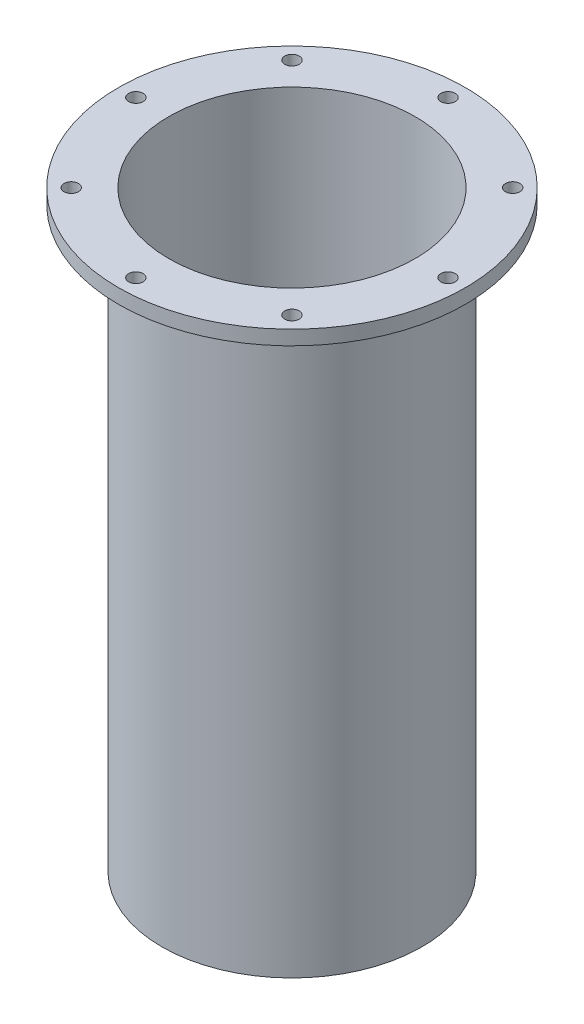
SolidWorks part; units mm, degrees
ref_plane "Front Plane" through (0, 0, 0) normal (0, 0, 1) x (1, 0, 0)
ref_plane "Top Plane" through (0, 0, 0) normal (0, 1, 0) x (1, 0, 0)
ref_plane "Right Plane" through (0, 0, 0) normal (1, 0, 0) x (0, 0, -1)
ref_axis "Axial" through (0, 55, 0) along (0, -1, 0)
sketch "Sketch1" plane through (0, 0, 0) normal (0, 1, 0) x (1, 0, 0)
  circle A0 centre (0, 0) radius 54.102
  circle A1 centre (0, 0) radius 57.15
  dimension "D1" = 114.3
  dimension "D2" = 108.204
extrude "Scheduled Chamber" add sketch "Sketch1" against normal blind 260.35
sketch "Sketch2" plane through (0, 0, 0) normal (0, 1, 0) x (1, 0, 0)
  circle A0 centre (0, 0) radius 54.102
  circle A1 centre (0, 0) radius 76.2
  dimension "D1" = 152.4
  dimension "D2" = 108.204
extrude "Flange" add sketch "Sketch2" against normal blind 6.35
sketch "Sketch3" plane through (0, 0, 0) normal (0, 1, 0) x (1, 0, 0)
  line L0 (0, -83.82) -> (0, 83.82) construction
  circle A0 centre (0, 68.58) radius 3.175
  dimension "D1" = 6.35
  dimension "D2" = 68.58
extrude "Original Bolt Hole" cut sketch "Sketch3" against normal up to next
pattern_circular "Bolt Hole Pattern" count 8 over 360 about axis through (0, 55, 0) along (0, -1, 0) of "Original Bolt Hole"
